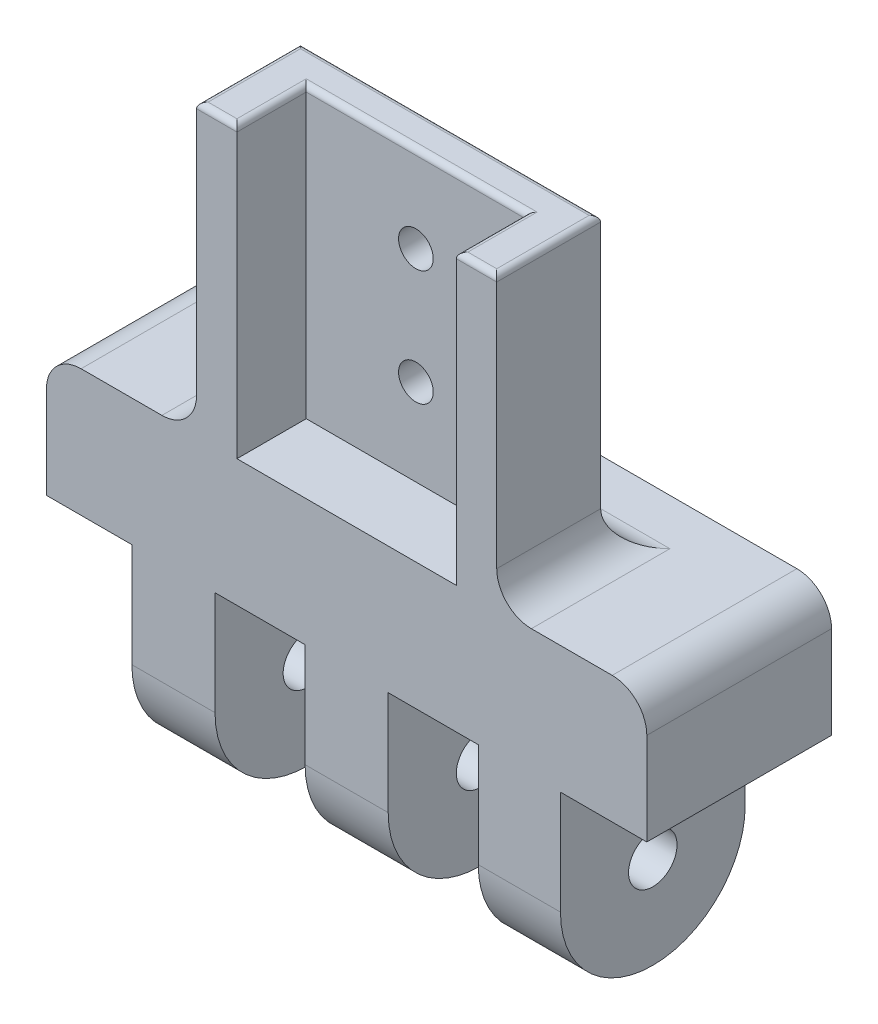
SolidWorks part; units mm, degrees
ref_plane "Front Plane" through (0, 0, 0) normal (0, 0, 1) x (1, 0, 0)
ref_plane "Top Plane" through (0, 0, 0) normal (0, 1, 0) x (1, 0, 0)
ref_plane "Right Plane" through (0, 0, 0) normal (1, 0, 0) x (0, 0, -1)
sketch "Sketch2" plane through (0, 0, 0) normal (1, 0, 0) x (0, 0, -1)
  line L2 (-8, 0) -> (-8, 20)
  line L3 (-8, 20) -> (8, 20)
  line L4 (8, 0) -> (8, 20)
  circle A0 centre (0, 0) radius 2.1
  arc A1 (-8, 0) -> (8, 0) centre (0, 0) ccw
  dimension "D1" = 16
  dimension "D2" = 4.2
  dimension "D3" = 20
extrude "Boss-Extrude1" add sketch "Sketch2" along normal mid plane 52
sketch "Sketch3" plane through (0, 0, 8) normal (0, 0, 1) x (1, 0, 0)
  line L0 (26, 0) -> (-26, 0) construction
  line L1 (-26, -9) -> (-18.6, -9)
  line L2 (-26, -9) -> (-26, 9)
  line L3 (-26, 9) -> (-18.6, 9)
  line L4 (-18.6, -9) -> (-18.6, 9)
  line L5 (-26, -9) -> (-18.6, 9) construction
  line L6 (-26, 9) -> (-18.6, -9) construction
  line L8 (-11.4, -9) -> (-3.6, -9)
  line L9 (-11.4, -9) -> (-11.4, 9)
  line L10 (-11.4, 9) -> (-3.6, 9)
  line L11 (-3.6, -9) -> (-3.6, 9)
  line L12 (-11.4, -9) -> (-3.6, 9) construction
  line L13 (-11.4, 9) -> (-3.6, -9) construction
  line L14 (3.6, -9) -> (11.4, -9)
  line L15 (3.6, -9) -> (3.6, 9)
  line L16 (3.6, 9) -> (11.4, 9)
  line L17 (11.4, -9) -> (11.4, 9)
  line L18 (3.6, -9) -> (11.4, 9) construction
  line L19 (3.6, 9) -> (11.4, -9) construction
  line L20 (-26, 20) -> (-26, 0) construction
  line L21 (26, 20) -> (26, 0) construction
  line L22 (18.519, -9) -> (26, -9)
  line L23 (18.519, -9) -> (18.519, 9)
  line L24 (18.519, 9) -> (26, 9)
  line L25 (26, -9) -> (26, 9)
  line L26 (18.519, -9) -> (26, 9) construction
  line L27 (18.519, 9) -> (26, -9) construction
  point P0 (-22.3, 0)
  point P7 (-7.5, 0)
  point P12 (7.5, 0)
  point P17 (-22.3, 9)
  point P20 (22.2595, 0)
  dimension "D1" = 9
  dimension "D4" = 7.2
  dimension "D6" = 7.2
  dimension "D2" = 7.8
  dimension "D3" = 14.6
extrude "Cut-Extrude1" cut sketch "Sketch3" against normal through all
ref_plane "Plane1" through (0, 20, 0) normal (0, 1, 0) x (1, 0, 0)
sketch "Sketch4" plane through (0, 20, 0) normal (0, 1, 0) x (1, 0, 0)
  line L0 (26, 8) -> (26, -8) construction
  line L1 (13, -8) -> (-13, -8)
  line L2 (13, -8) -> (13, 1)
  line L3 (13, 1) -> (-13, 1)
  line L4 (-13, -8) -> (-13, 1)
  line L5 (13, -8) -> (-13, 1) construction
  line L6 (13, 1) -> (-13, -8) construction
  line L8 (26, -8) -> (-26, -8) construction
  point P0 (0, -3.5)
  point P7 (0, 0)
  point P8 (0, 0)
  dimension "D1" = 26
  dimension "D2" = 9
  dimension "D3" = 26
extrude "Boss-Extrude2" add sketch "Sketch4" along normal blind 25
ref_plane "Plane2" through (0, 45, 0) normal (0, 1, 0) x (1, 0, 0)
sketch "Sketch5" plane through (0, 45, 0) normal (0, 1, 0) x (1, 0, 0)
  line L0 (13, -8) -> (13, 1) construction
  line L1 (-9.5, -2) -> (9.5, -2)
  line L2 (-9.5, -2) -> (-9.5, -8)
  line L3 (-9.5, -8) -> (9.5, -8)
  line L4 (9.5, -2) -> (9.5, -8)
  line L5 (-9.5, -2) -> (9.5, -8) construction
  line L6 (-9.5, -8) -> (9.5, -2) construction
  line L7 (-13, -8) -> (13, -8) construction
  point P0 (0, -5)
  dimension "D1" = 19
  dimension "D2" = 13
  dimension "D3" = 6
extrude "Cut-Extrude2" cut sketch "Sketch5" against normal blind 25
fillet "Fillet1" radius 3 3 edges at (13, 20, 3.5) (0, 20, -1) (-13, 20, 3.5)
fillet "Fillet2" radius 3 2 edges at (26, 20, 0) (-26, 20, 0)
fillet "Fillet3" radius 0.5 8 edges at (13, 45, 3.5) (9.5, 45, 5) (11.25, 45, 8) (-11.25, 45, 8) (-9.5, 45, 5) (0, 45, 2) (0, 45, -1) (-13, 45, 3.5)
sketch "Sketch6" plane through (0, 0, 0) normal (0, 0, 1) x (1, 0, 0)
  line L0 (9.5, 20) -> (9.5, 44.5) construction
  line L1 (-16.3932, 32.5) -> (15.2785, 32.5) construction
  line L2 (9.5, 20) -> (-9.5, 20) construction
  circle A0 centre (0, 37.5) radius 1.5
  circle A1 centre (0, 27.5) radius 1.5
  dimension "D1" = 3
  dimension "D2" = 9.5
  dimension "D3" = 10
  dimension "D4" = 5
  dimension "D5" = 12.5
extrude "Cut-Extrude3" cut sketch "Sketch6" against normal mid plane 25
equation "\"hingewidth\"=7.2"
equation "\"fingerwidth\"=10.5"
equation "\"gapwidth\"=7.4"
equation "\"D4@Sketch3\"=\"hingewidth\""
equation "\"D6@Sketch3\"=\"hingewidth\""
